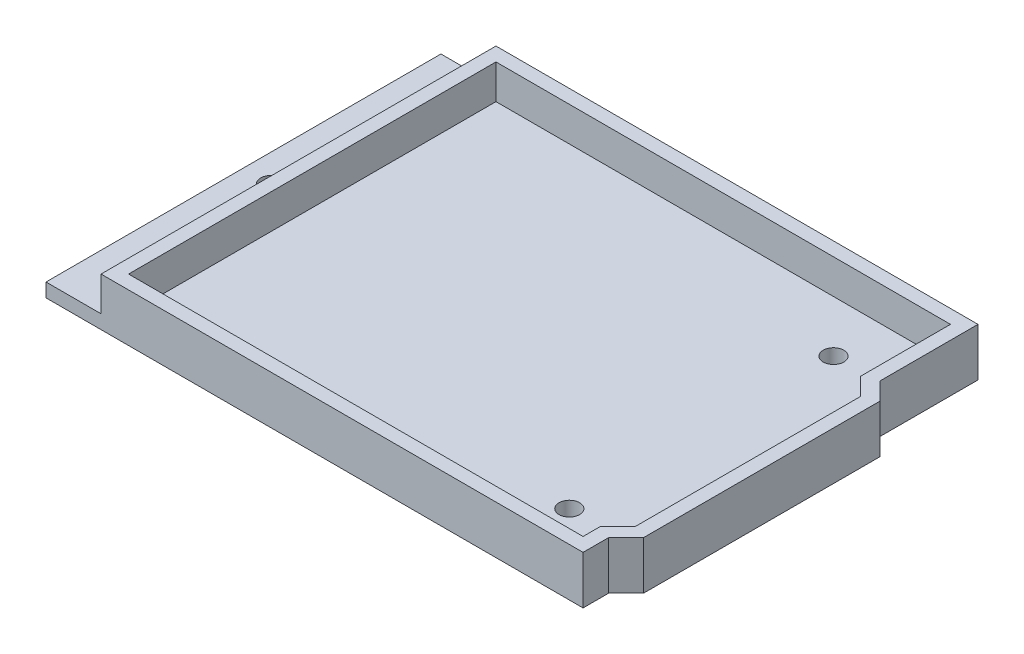
SolidWorks part; units mm, degrees
ref_plane "Front Plane" through (0, 0, 0) normal (0, 0, 1) x (1, 0, 0)
ref_plane "Top Plane" through (0, 0, 0) normal (0, 1, 0) x (1, 0, 0)
ref_plane "Right Plane" through (0, 0, 0) normal (1, 0, 0) x (0, 0, -1)
sketch "Sketch1" plane through (0, 0, 0) normal (0, 1, 0) x (1, 0, 0)
  line L0 (35.9267, -1.726) -> (38.4667, -4.266)
  line L1 (-30.1333, 11.324) -> (35.9267, 11.324)
  line L2 (-30.1333, 11.324) -> (-30.1333, -42.076)
  line L3 (-30.1333, -42.076) -> (35.9267, -42.076)
  line L4 (35.9267, 11.324) -> (35.9267, -1.726)
  line L5 (38.4667, -4.266) -> (38.4667, -36.996)
  line L6 (38.4667, -36.996) -> (35.9267, -39.536)
  line L7 (35.9267, -39.536) -> (35.9267, -42.076)
  line L8 (37.9267, -44.076) -> (37.9267, -40.3645)
  line L9 (-32.1333, 13.324) -> (37.9267, 13.324)
  line L10 (-32.1333, 13.324) -> (-32.1333, -44.076)
  line L11 (-32.1333, -44.076) -> (37.9267, -44.076)
  line L12 (40.4667, -3.4376) -> (40.4667, -37.8245)
  line L13 (37.9267, -40.3645) -> (40.4667, -37.8245)
  line L14 (37.9267, 13.324) -> (37.9267, -0.8976)
  line L15 (37.9267, -0.8976) -> (40.4667, -3.4376)
  line L16 (35.9267, -1.726) -> (37.9267, -0.8976)
  line L17 (35.9267, -39.536) -> (35.9267, -1.726) construction
  line L18 (-32.1333, 13.324) -> (-40.1333, 13.324)
  line L19 (-32.1333, 13.324) -> (-32.1333, -44.076)
  line L20 (-32.1333, -44.076) -> (-40.1333, -44.076)
  line L21 (-40.1333, 13.324) -> (-40.1333, -44.076)
  dimension "D1" = 53.4
  dimension "D2" = 68.6
  dimension "D3" = 135
  dimension "D4" = 135
  dimension "D5" = 2.54
  dimension "D6" = 32.73
  dimension "D7" = 2
  dimension "D8" = 2
  dimension "D9" = 2
  dimension "D10" = 2
  dimension "D11" = 2
  dimension "D12" = 2
  dimension "D13" = 2
  dimension "D14" = 8
  dimension "D15" = 2.54
extrude "Boss-Extrude1" add sketch "Sketch1" along normal blind 7 contours L6 L7 L3 L2 L1 L4 L14 L9 L10 L11 L8 L13 L12 L15 L0 L5 region at (38.5423, 0, 2.822)
sketch "Sketch2" plane through (0, 0, 0) normal (0, 1, 0) x (1, 0, 0)
  line L0 (-30.1333, 11.324) -> (35.9267, 11.324)
  line L1 (35.9267, 11.324) -> (35.9267, -1.726)
  line L2 (35.9267, -1.726) -> (38.4667, -4.266)
  line L3 (38.4667, -4.266) -> (38.4667, -36.996)
  line L4 (38.4667, -36.996) -> (35.9267, -39.536)
  line L5 (35.9267, -39.536) -> (35.9267, -42.076)
  line L6 (35.9267, -42.076) -> (-30.1333, -42.076)
  line L7 (-30.1333, -42.076) -> (-30.1333, 11.324)
extrude "Boss-Extrude2" add sketch "Sketch2" along normal blind 2
sketch "Sketch3" plane through (0, 0, 0) normal (0, 1, 0) x (1, 0, 0)
  line L0 (-32.1333, 13.324) -> (-40.1333, 13.324)
  line L1 (-40.1333, 13.324) -> (-40.1333, -44.076)
  line L2 (-40.1333, -44.076) -> (-32.1333, -44.076)
  line L3 (-32.1333, -44.076) -> (-32.1333, 13.324)
  dimension "D1" = 8
extrude "Boss-Extrude3" add sketch "Sketch3" along normal blind 2
sketch "Sketch4" plane through (0, 2, 0) normal (0, 1, 0) x (1, 0, 0)
  line L0 (35.9267, 11.324) -> (-30.1333, 11.324) construction
  line L1 (-30.1333, -42.076) -> (35.9267, -42.076) construction
  line L2 (35.9267, -1.726) -> (35.9267, 11.324) construction
  line L3 (-36.1333, 13.324) -> (-36.1333, -44.076)
  line L4 (-32.1333, 13.324) -> (-40.1333, 13.324) construction
  line L5 (-40.1333, -44.076) -> (-32.1333, -44.076) construction
  circle A0 centre (26.4267, 3.824) radius 1.5
  circle A1 centre (26.4267, -34.576) radius 1.5
  circle A2 centre (-36.1333, -15.376) radius 1.5
  point P0 (26.4267, 3.824)
  point P1 (26.4267, -34.576)
  dimension "D4" = 3
  dimension "D1" = 7.5
  dimension "D2" = 7.5
  dimension "D3" = 9.5
extrude "Cut-Extrude1" cut sketch "Sketch4" against normal through all contours A0 | A1 | L3 A2 | L3 A2 region at (-35.4967, 2, 15.376) region at (-36.7699, 2, 15.376) region at (26.4267, 2, -3.824) region at (26.4267, 2, 34.576)
sketch "Sketch5" plane through (0, 0, 0) normal (0, -1, 0) x (1, 0, 0)
  circle A0 centre (26.4267, 34.576) radius 3
  circle A1 centre (26.4267, -3.824) radius 3
  circle A2 centre (-36.1333, 15.376) radius 3
  circle A3 centre (26.4267, 34.576) radius 1.5
  circle A4 centre (26.4267, -3.824) radius 1.5
  circle A5 centre (-36.1333, 15.376) radius 1.5
  dimension "D1" = 6
extrude "Boss-Extrude4" add sketch "Sketch5" along normal blind 1
fillet "Fillet1" radius 0.5 1 edges at (-36.1333, -1, 12.376)
fillet "Fillet2" radius 0.5 1 edges at (26.4267, -1, -6.824)
fillet "Fillet3" radius 0.5 1 edges at (26.4267, -1, 31.576)
